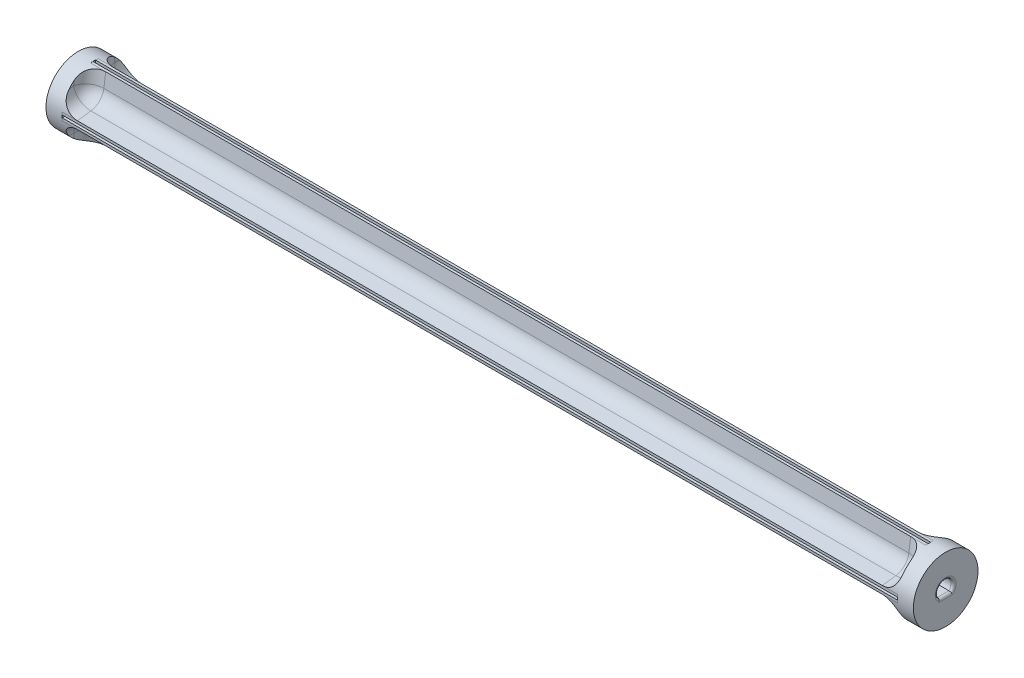
SolidWorks part; units mm, degrees
material "Custom Plastic"
ref_plane "Front Plane" through (0, 0, 0) normal (0, 0, 1) x (1, 0, 0)
ref_plane "Top Plane" through (0, 0, 0) normal (0, 1, 0) x (1, 0, 0)
ref_plane "Right Plane" through (0, 0, 0) normal (1, 0, 0) x (0, 0, -1)
sketch "Sketch1" plane through (0, 0, 0) normal (1, 0, 0) x (0, 0, -1)
  line L2 (6.3451, 0.25) -> (0.25, 0.25)
  line L3 (0.25, 0.25) -> (0.25, 6.3451)
  line L4 (0, 0) -> (6.35, 0) construction
  line L17 (0.25, 6.3451) -> (0.75, 6.3451)
  line L18 (0.75, 6.3451) -> (1.4142, 1.4142)
  line L19 (1.4142, 1.4142) -> (6.3451, 0.75)
  line L20 (6.3451, 0.75) -> (6.3451, 0.25)
  line L21 (0.75, -6.3451) -> (0.25, -6.3451)
  line L22 (0.25, -6.3451) -> (0.25, -0.25)
  line L23 (0.25, -0.25) -> (6.3451, -0.25)
  line L24 (6.3451, -0.25) -> (6.3451, -0.75)
  line L25 (6.3451, -0.75) -> (1.4142, -1.4142)
  line L26 (1.4142, -1.4142) -> (0.75, -6.3451)
  line L27 (-6.3451, -0.75) -> (-6.3451, -0.25)
  line L28 (-6.3451, -0.25) -> (-0.25, -0.25)
  line L29 (-0.25, -0.25) -> (-0.25, -6.3451)
  line L30 (-0.25, -6.3451) -> (-0.75, -6.3451)
  line L31 (-0.75, -6.3451) -> (-1.4142, -1.4142)
  line L32 (-1.4142, -1.4142) -> (-6.3451, -0.75)
  line L33 (-0.75, 6.3451) -> (-0.25, 6.3451)
  line L34 (-0.25, 6.3451) -> (-0.25, 0.25)
  line L35 (-0.25, 0.25) -> (-6.3451, 0.25)
  line L36 (-6.3451, 0.25) -> (-6.3451, 0.75)
  line L37 (-6.3451, 0.75) -> (-1.4142, 1.4142)
  line L38 (-1.4142, 1.4142) -> (-0.75, 6.3451)
  circle A0 centre (0, 0) radius 6.35 construction
  circle A1 centre (0, 0) radius 2
  point P4 (0, 0)
  point P11 (0, 0)
  point P23 (0, 0)
  point P33 (0, 0)
  dimension "D1" = 12.7
  dimension "D5" = 4
  dimension "D2" = 0.5
  dimension "D3" = 0.5
  dimension "D4" = 2
  dimension "D7" = 4.35
  dimension "D6" = 4
extrude "Boss-Extrude1" add sketch "Sketch1" along normal mid plane 165.1 contours L2 A1 L3 | A1 L2 L3 | A1 | A1 | A1 | A1 | A1 | A1 | A1 | L20 L2 L3 L17 L18 L19 | L21 L22 L23 L24 L25 L26 | L27 L28 L29 L30 L31 L32 | L33 L34 L35 L36 L37 L38 region at (0, 0.9584, -0.9584) region at (0, 3.7736, -0.6885) region at (0, -0.9584, -0.9584) region at (0, 3.7736, 0.6885) region at (0, 0.9584, 0.9584) region at (0, -3.7736, -0.6885) region at (0, -0.9584, 0.9584) region at (0, -3.7736, 0.6885)
fillet "Fillet2" radius 3 4 edges at (0, -1.4142, 1.4142) (0, -1.4142, -1.4142) (0, 1.4142, -1.4142) (0, 1.4142, 1.4142)
sketch "Sketch2" plane through (82.55, 0, 0) normal (1, 0, 0) x (0, 0, -1)
  circle A0 centre (0, 0) radius 6.3892
extrude "Boss-Extrude2" add sketch "Sketch2" along normal blind 3.175
fillet "Fillet3" radius 3 12 edges at (82.55, 5.0133, -0.9294) (82.55, 1.9606, -1.9606) (82.55, 5.0133, 0.9294) (82.55, 0.9294, 5.0133) (82.55, -0.9294, 5.0133) (82.55, -5.0133, 0.9294) (82.55, -5.0133, -0.9294) (82.55, -1.9606, -1.9606) (82.55, 0.9294, -5.0133) (82.55, 1.9606, 1.9606) (82.55, -1.9606, 1.9606) (82.55, -0.9294, -5.0133)
mirror "Mirror1" about plane through (0, 0, 0) normal (1, 0, 0) of "Boss-Extrude2", "Fillet3"
sketch "Sketch3" plane through (85.725, 0, 0) normal (1, 0, 0) x (0, 0, -1)
  line L0 (-1.12, -0.9978) -> (1.12, -0.9978)
  line L1 (-1.1422, -1.0478) -> (1.1422, -1.0478)
  arc A0 (1.12, -0.9978) -> (-1.12, -0.9978) centre (0, 0) ccw
  arc A1 (1.1422, -1.0478) -> (-1.1422, -1.0478) centre (0, 0) ccw
  dimension "D1" = 3
  dimension "D2" = 2.24
  dimension "D3" = 0.05
extrude "Cut-Extrude1" cut sketch "Sketch3" against normal blind 10 contours L0 A0 | L1 A1 A0 L0 region at (85.725, 0.1489, 0) region at (85.725, 1.5096, 0)
fillet "Fillet4" radius 0.5 2 edges at (85.725, -1.0478, 0) (85.725, 1.55, 0)
sketch "Sketch4" plane through (-85.725, 0, 0) normal (-1, 0, 0) x (0, 0, 1)
  circle A0 centre (0, 0) radius 1.5
  dimension "D1" = 3
extrude "Cut-Extrude2" cut sketch "Sketch4" against normal blind 25
equation "\"D1@Sketch1\"=.5in"
equation "\"D1@Boss-Extrude1\"=6.5in"
equation "\"D1@Boss-Extrude2\"=.125in"
